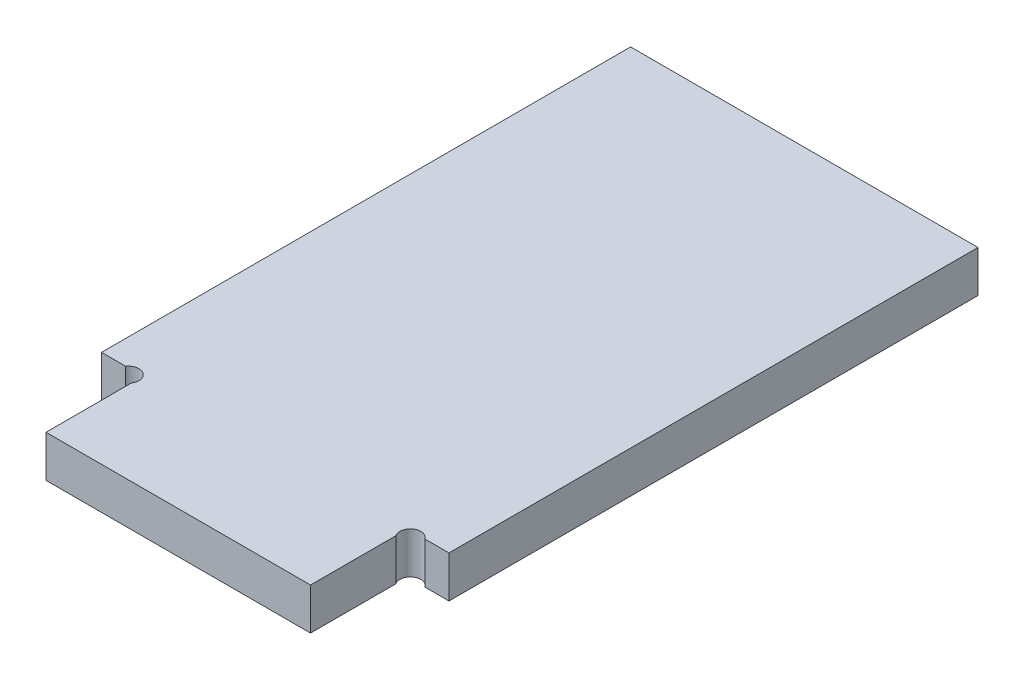
SolidWorks part; units mm, degrees
ref_plane "Front Plane" through (0, 0, 0) normal (0, 0, 1) x (1, 0, 0)
ref_plane "Top Plane" through (0, 0, 0) normal (0, 1, 0) x (1, 0, 0)
ref_plane "Right Plane" through (0, 0, 0) normal (1, 0, 0) x (0, 0, -1)
sketch "Sketch1" plane through (0, 0, 0) normal (0, 1, 0) x (1, 0, 0)
  line L0 (-1.905, -0.167) -> (-1.905, -1.397)
  line L1 (-1.905, -1.397) -> (1.905, -1.397)
  line L3 (-2.1542, 0) -> (-2.5019, 0)
  line L4 (-2.5019, 0) -> (-2.5019, 7.62)
  line L5 (-2.5019, 7.62) -> (2.5019, 7.62)
  line L6 (0, 7.62) -> (0, -1.397) construction
  line L7 (2.5019, 0) -> (2.5019, 7.62)
  line L8 (2.1542, 0) -> (2.5019, 0)
  line L9 (1.905, -0.167) -> (1.905, -1.397)
  line L10 (-1.8796, -0.0835) -> (-1.905, -0.0835) construction
  arc A0 (-1.905, -0.167) -> (-2.1542, 0) centre (-2.0296, -0.0835) ccw
  arc A1 (1.905, -0.167) -> (2.1542, 0) centre (2.0296, -0.0835) cw
  point P15 (0, 0)
  point P18 (-1.905, 0)
  dimension "D4" = 0.3
  dimension "D1" = 3.81
  dimension "D2" = 1.397
  dimension "D3" = 5.0038
  dimension "D5" = 7.62
  dimension "D6" = 0.0254
extrude "Boss-Extrude1" add sketch "Sketch1" along normal mid plane 0.6
